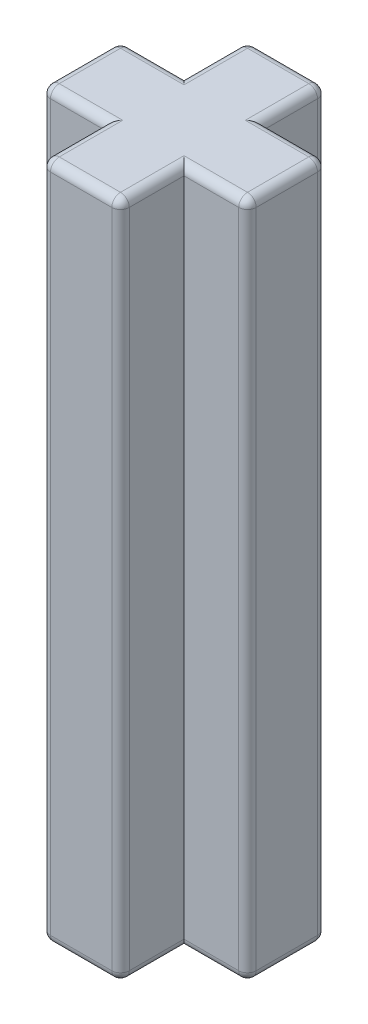
SolidWorks part; units mm, degrees
ref_plane "Front Plane" through (0, 0, 0) normal (0, 0, 1) x (1, 0, 0)
ref_plane "Top Plane" through (0, 0, 0) normal (0, 1, 0) x (1, 0, 0)
ref_plane "Right Plane" through (0, 0, 0) normal (1, 0, 0) x (0, 0, -1)
sketch "Sketch1" plane through (0, 0, 0) normal (0, 1, 0) x (1, 0, 0)
  line L0 (-0.9, 0.9) -> (-0.9, 2.35)
  line L1 (-0.9, -2.35) -> (0.9, -2.35)
  line L2 (-0.9, -2.35) -> (-0.9, -0.9)
  line L3 (-0.9, 2.35) -> (0.9, 2.35)
  line L4 (0.9, -2.35) -> (0.9, -0.9)
  line L5 (-0.9, -2.35) -> (0.9, 2.35) construction
  line L6 (-0.9, 2.35) -> (0.9, -2.35) construction
  line L7 (2.35, 0.9) -> (0.9, 0.9)
  line L8 (2.35, 0.9) -> (2.35, -0.9)
  line L9 (2.35, -0.9) -> (0.9, -0.9)
  line L10 (-2.35, 0.9) -> (-2.35, -0.9)
  line L11 (2.35, 0.9) -> (-2.35, -0.9) construction
  line L12 (2.35, -0.9) -> (-2.35, 0.9) construction
  line L13 (-0.9, -0.9) -> (-2.35, -0.9)
  line L14 (0.9, 0.9) -> (0.9, 2.35)
  line L15 (-0.9, 0.9) -> (-2.35, 0.9)
  point P0 (0, 0)
  point P6 (0, 0)
  dimension "D1" = 4.7
  dimension "D2" = 1.8
  dimension "D3" = 4.7
extrude "Boss-Extrude1" add sketch "Sketch1" along normal blind 15.5
fillet "Fillet1" radius 0.2 12 edges at (1.625, 15.5, -0.9) (2.35, 15.5, 0) (1.625, 15.5, 0.9) (0.9, 15.5, 1.625) (0, 15.5, 2.35) (-0.9, 15.5, 1.625) (-1.625, 15.5, 0.9) (-2.35, 15.5, 0) (-1.625, 15.5, -0.9) (-0.9, 15.5, -1.625) (0, 15.5, -2.35) (0.9, 15.5, -1.625)
fillet "Fillet2" radius 0.2 12 edges at (0, 0, -2.35) (-0.9, 0, -1.625) (-1.625, 0, -0.9) (-2.35, 0, 0) (-1.625, 0, 0.9) (-0.9, 0, 1.625) (0, 0, 2.35) (0.9, 0, 1.625) (1.625, 0, 0.9) (2.35, 0, 0) (1.625, 0, -0.9) (0.9, 0, -1.625)
fillet "Fillet3" radius 0.2 24 edges at (2.2914, 15.4414, -0.8414) (2.2914, 0.0586, -0.8414) (2.2914, 15.4414, 0.8414) (2.2914, 0.0586, 0.8414) (-0.8414, 15.4414, -2.2914) (-0.8414, 0.0586, -2.2914) (0.8414, 15.4414, -2.2914) (0.8414, 0.0586, -2.2914) (0.8414, 15.4414, 2.2914) (0.8414, 0.0586, 2.2914) (-0.8414, 15.4414, 2.2914) (-0.8414, 0.0586, 2.2914) (-2.2914, 15.4414, 0.8414) (-2.2914, 0.0586, 0.8414) (-2.2914, 15.4414, -0.8414) (-2.2914, 0.0586, -0.8414) (2.35, 7.75, -0.9) (2.35, 7.75, 0.9) (-0.9, 7.75, -2.35) (0.9, 7.75, -2.35) (0.9, 7.75, 2.35) (-0.9, 7.75, 2.35) (-2.35, 7.75, 0.9) (-2.35, 7.75, -0.9)
